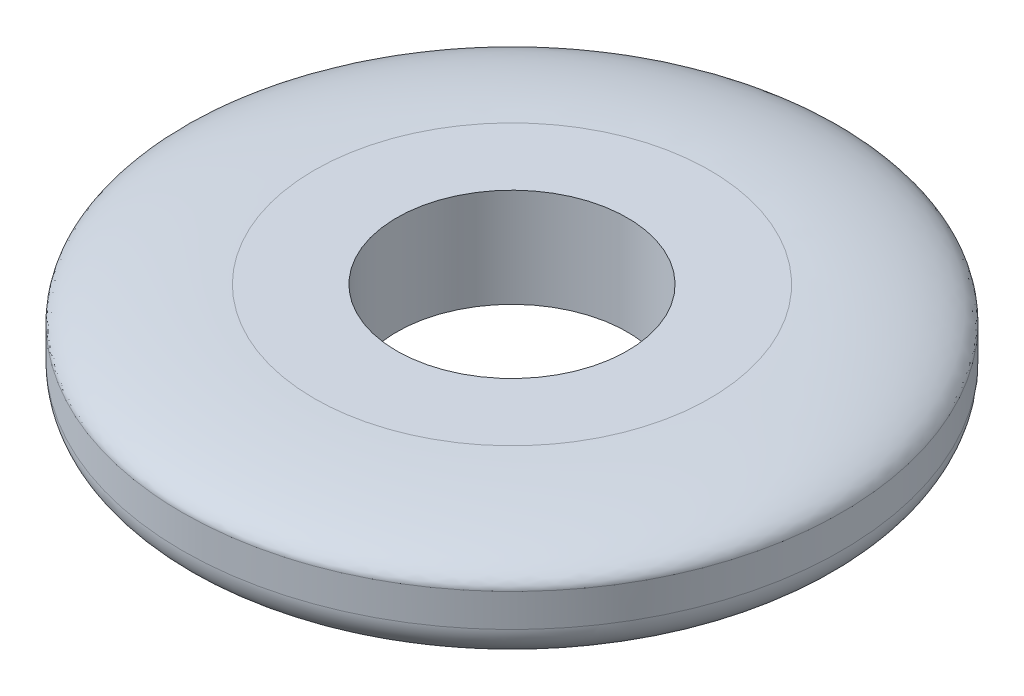
SolidWorks part; units mm, degrees
ref_plane "Front Plane" through (0, 0, 0) normal (0, 0, 1) x (1, 0, 0)
ref_plane "Top Plane" through (0, 0, 0) normal (0, 1, 0) x (1, 0, 0)
ref_plane "Right Plane" through (0, 0, 0) normal (1, 0, 0) x (0, 0, -1)
sketch "Sketch1" plane through (0, 0, 0) normal (0, 1, 0) x (1, 0, 0)
  circle A0 centre (0, 0) radius 3.5
  circle A1 centre (0, 0) radius 10
  dimension "D1" = 7
  dimension "D2" = 20
extrude "Boss-Extrude1" add sketch "Sketch1" along normal blind 3
fillet "Fillet1" radius 1 1 edges at (0, 3, 10) second distance 4 first distance on face at (0, 3, 10)
fillet "Fillet2" radius 1 1 edges at (0, 0, 10)
